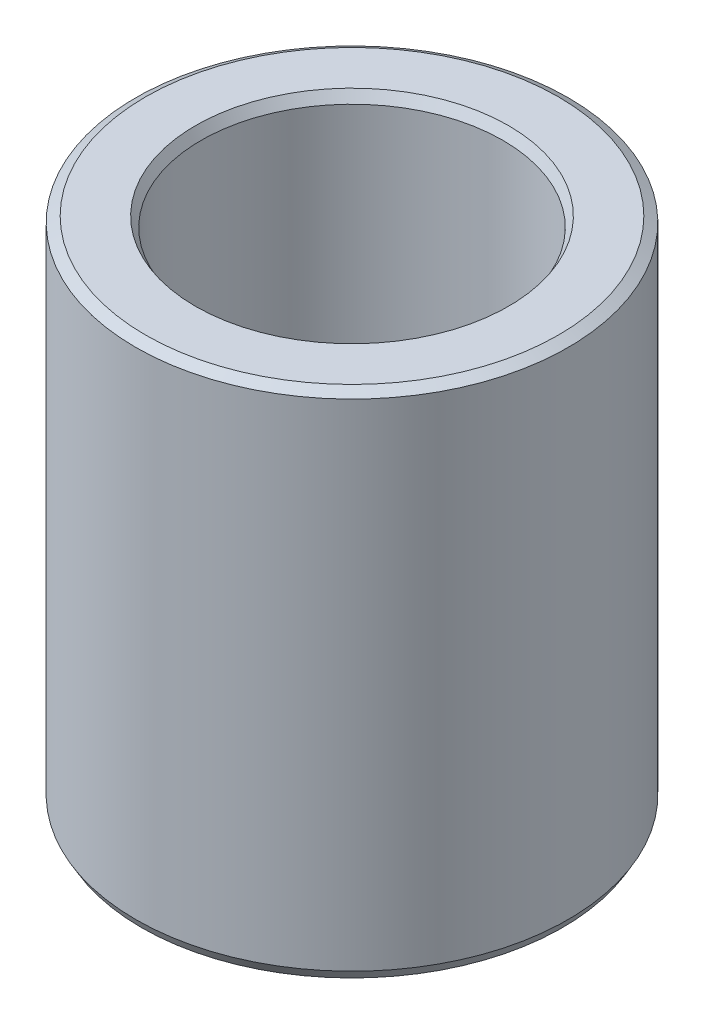
SolidWorks part; units mm, degrees
ref_plane "Front Plane" through (0, 0, 0) normal (0, 0, 1) x (1, 0, 0)
ref_plane "Top Plane" through (0, 0, 0) normal (0, 1, 0) x (1, 0, 0)
ref_plane "Right Plane" through (0, 0, 0) normal (1, 0, 0) x (0, 0, -1)
sketch "Sketch1" plane through (0, 0, 0) normal (0, 1, 0) x (1, 0, 0)
  circle A0 centre (0, 0) radius 30
  dimension "SLEEVE_OD" = 60
extrude "Boss-Extrude1" add sketch "Sketch1" along normal blind 70.8984
sketch "Sketch2" plane through (0, 0, 0) normal (0, 1, 0) x (1, 0, 0)
  circle A0 centre (0, 0) radius 20.9255
  dimension "BORE_D" = 41.851
extrude "Cut-Extrude1" cut sketch "Sketch2" along normal through all
chamfer "Chamfer1" distance 0.7913 angle 60 4 edges at (0, 70.8984, 20.9255) (0, 0, 20.9255) (0, 0, 30) (0, 70.8984, 30) first distance on face at (0, 70.8984, 20.9255) first distance on face at (0, 0, 20.9255) first distance on face at (0, 70.8984, 30)
